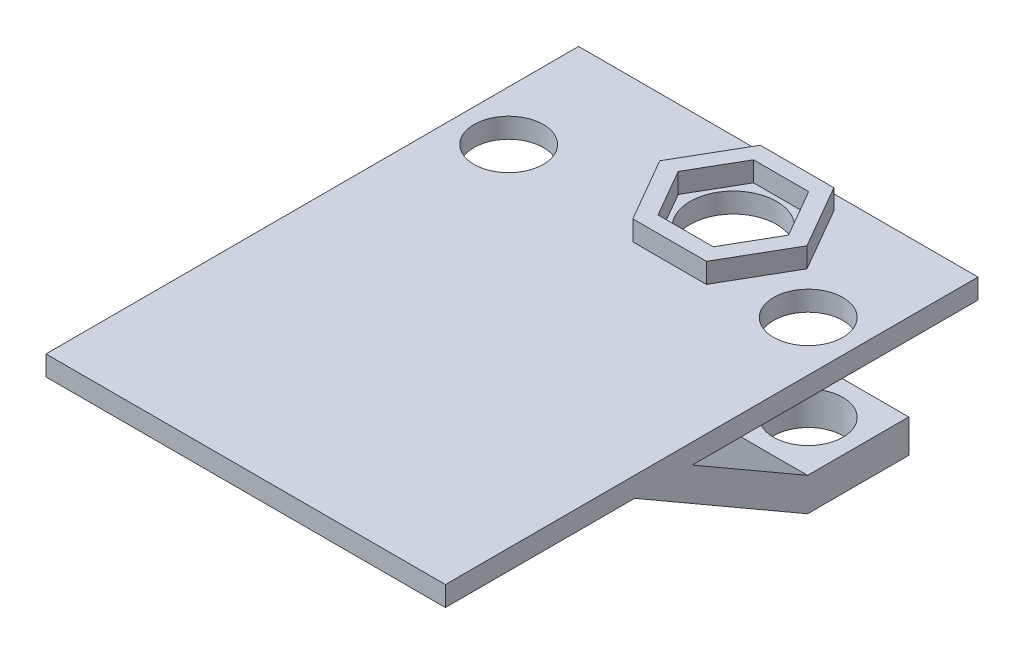
SolidWorks part; units mm, degrees
ref_plane "Front Plane" through (0, 0, 0) normal (0, 0, 1) x (1, 0, 0)
ref_plane "Top Plane" through (0, 0, 0) normal (0, 1, 0) x (1, 0, 0)
ref_plane "Right Plane" through (0, 0, 0) normal (1, 0, 0) x (0, 0, -1)
sketch "Sketch1" plane through (0, 0, 0) normal (0, 1, 0) x (1, 0, 0)
  line L0 (-22.5, 22) -> (22.5, 22) construction
  line L1 (30, -40) -> (-30, -40)
  line L2 (30, -40) -> (30, 40)
  line L3 (30, 40) -> (-30, 40)
  line L4 (-30, -40) -> (-30, 40)
  line L5 (30, -40) -> (-30, 40) construction
  line L6 (30, 40) -> (-30, -40) construction
  line L7 (0.8875, 35.395) -> (-3.255, 28.22)
  line L8 (-3.255, 28.22) -> (0.8875, 21.045)
  line L9 (0.8875, 21.045) -> (9.1725, 21.045)
  line L10 (9.1725, 21.045) -> (13.315, 28.22)
  line L11 (13.315, 28.22) -> (9.1725, 35.395)
  line L12 (9.1725, 35.395) -> (0.8875, 35.395)
  line L13 (10.5581, 18.645) -> (16.0863, 28.22)
  line L14 (16.0863, 28.22) -> (10.5581, 37.795)
  line L15 (10.5581, 37.795) -> (-0.4981, 37.795)
  line L16 (-0.4981, 37.795) -> (-6.0263, 28.22)
  line L17 (-6.0263, 28.22) -> (-0.4981, 18.645)
  line L18 (-0.4981, 18.645) -> (10.5581, 18.645)
  circle A1 centre (5.03, 28.22) radius 7.175 construction
  circle A2 centre (-22.5, 22) radius 5.2
  circle A3 centre (22.5, 22) radius 5.2
  circle A4 centre (5.03, 28.22) radius 6.5
  circle A5 centre (-22.5, 22) radius 7.6
  circle A6 centre (22.5, 22) radius 7.6
  point P0 (0, 0)
  point P18 (0, 22)
  dimension "D4" = 10.4
  dimension "D5" = 10.4
  dimension "D10" = 13
  dimension "D1" = 60
  dimension "D2" = 80
  dimension "D3" = 14.35
  dimension "D6" = 45
  dimension "D7" = 17.47
  dimension "D8" = 6.22
  dimension "D9" = 18
  dimension "D11" = 2.4
  dimension "D12" = 2.4
  dimension "D13" = 2.4
sketch "Sketch2" plane through (0, 0, 0) normal (1, 0, 0) x (0, 0, -1)
  line L0 (27.2, 0) -> (16.8, 0) construction
  line L1 (29.6, 0) -> (14.4, 0) construction
  line L2 (27.2, 0) -> (16.8, 0)
  line L3 (29.6, 0) -> (14.4, 0)
  line L4 (-40, 0) -> (40, 0) construction
  line L5 (-40, 0) -> (40, 0)
  line L6 (-2.9205, 0) -> (14.4, -10)
  line L7 (14.4, -10) -> (29.6, -10)
  line L8 (29.6, -10) -> (29.6, -15)
  line L9 (29.6, -15) -> (14.4, -15)
  line L10 (14.4, -15) -> (-11.5808, 0)
  line L11 (-2.9205, 0) -> (-11.5808, 0)
  point P10 (22, 0)
  point P13 (22, -10)
  point P14 (22, -15)
  dimension "D1" = 5
  dimension "D2" = 30
  dimension "D3" = 10
extrude "Boss-Extrude4" add sketch "Sketch1" along normal blind 3 contours A6 L2 L3 L4 A5 L1 L18 L17 L16 L15 L14 L13 | L2 A6 A3 | L4 A5 A2 | A2 | A3 | L17 L18 L13 L14 L15 L16 L12 L11 L10 L9 L8 L7 | L11 L12 L7 L8 L9 L10 A4 region at (-0.3878, 0, 4.1117) region at (15.1143, 0, -22) region at (-29.7857, 0, -22) region at (5.03, 0, -35.1758) region at (5.03, 0, -18.9375) region at (-22.5, 0, -22) region at (22.5, 0, -22)
extrude "Boss-Extrude5" add sketch "Sketch2" against normal blind 15 from surface contours L10 L9 L8 L7 L6 L5 region at (0, -8.8769, -11.0899) starting at face at (30, 1.5, 0)
extrude "Boss-Extrude6" add sketch "Sketch2<3>" along normal blind 15 from surface contours L10 L9 L8 L7 L6 L5 region at (0, -8.8769, -11.0899) starting at face at (-30, 1.5, 0)
sketch "Sketch2<3>" plane through (0, 0, 0) normal (1, 0, 0) x (0, 0, -1) same geometry as "Sketch2"
extrude "Boss-Extrude7" add sketch "Sketch1<6>" along normal blind 6 contours L17 L18 L13 L14 L15 L16 L12 L11 L10 L9 L8 L7 region at (5.03, 0, -18.9375)
sketch "Sketch1<6>" plane through (0, 0, 0) normal (0, 1, 0) x (1, 0, 0) same geometry as "Sketch1"
extrude "Cut-Extrude1" cut sketch "Sketch1<7>" against normal through all and the other way through all contours A3 | A2
sketch "Sketch1<7>" plane through (0, 0, 0) normal (0, 1, 0) x (1, 0, 0) same geometry as "Sketch1"
